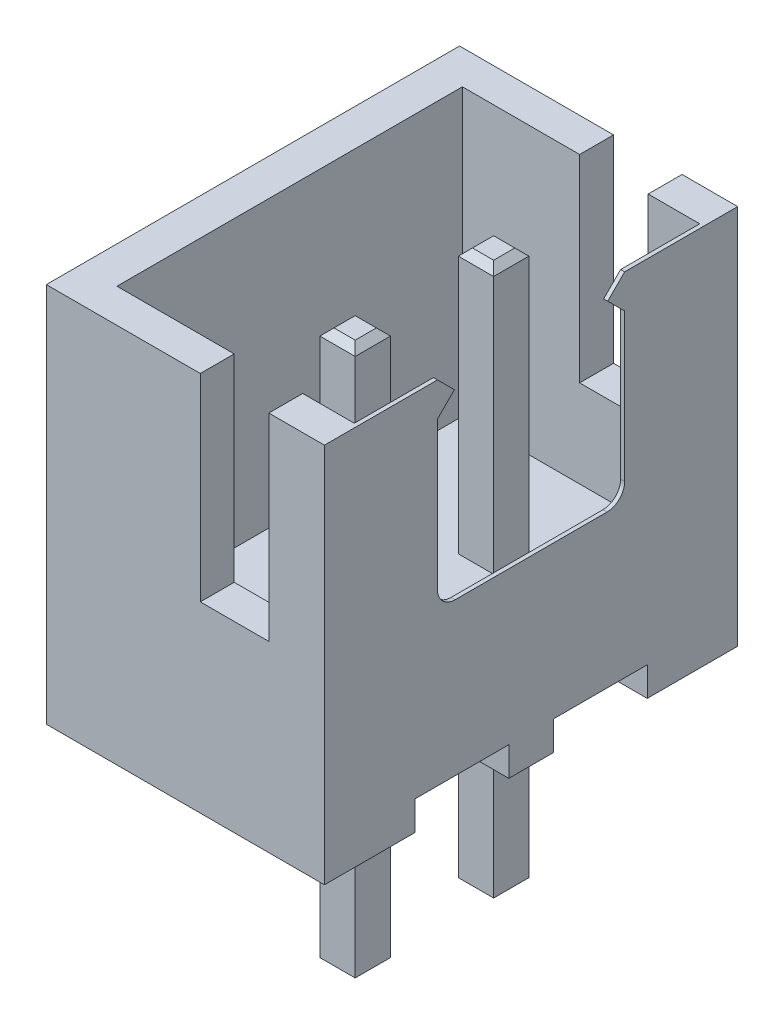
SolidWorks part; units mm, degrees
ref_plane "Front Plane" through (0, 0, 0) normal (0, 0, 1) x (1, 0, 0)
ref_plane "Top Plane" through (0, 0, 0) normal (0, 1, 0) x (1, 0, 0)
ref_plane "Right Plane" through (0, 0, 0) normal (1, 0, 0) x (0, 0, -1)
ref_plane "Plane1" through (-5.7277, 0, 0) normal (-1, 0, 0) x (0, -1, 0)
sketch "Sketch1" plane through (-5.7277, 0, 0) normal (-1, 0, 0) x (0, -1, 0)
  line L0 (-6.8453, -7.4295) -> (0, -7.4295)
  line L1 (0, -7.4295) -> (0, 0)
  line L2 (0, 0) -> (-6.8453, 0)
  line L3 (-6.8453, 0) -> (-6.8453, -7.4295)
extrude "Boss-Extrude1" add sketch "Sketch1" against normal blind 5
sketch "Sketch2" plane through (-5.7277, 0, 0) normal (-1, 0, 0) x (0, 0, 1)
  line L0 (-7.4295, 0) -> (-1.6256, 0)
  line L1 (-1.6256, 0) -> (-1.6256, 0.127)
  line L2 (-1.6256, 0.127) -> (-7.4295, 0.127)
  line L3 (-7.4295, 0.127) -> (-7.4295, 0)
extrude "Cut-Extrude1" cut sketch "Sketch2" against normal blind 5.7277
ref_plane "Plane2" through (0, 0, -1.6256) normal (0, 0, 1) x (1, 0, 0)
sketch "Sketch3" plane through (0, 0, -1.6256) normal (0, 0, 1) x (1, 0, 0)
  line L0 (-5.7277, 0.127) -> (-3.3477, 0.127)
  line L1 (-3.3477, 0.127) -> (-5.7277, 0.762)
  line L2 (-5.7277, 0.762) -> (-5.7277, 0.127)
  dimension "D1" = 2.38
extrude "Cut-Extrude2" cut sketch "Sketch3" against normal blind 1.6891
sketch "Sketch4" plane through (0, 0, -1.6256) normal (0, 0, 1) x (1, 0, 0)
  line L0 (-1.94, 0.127) -> (0, 0.127)
  line L1 (0, 0.127) -> (0, 0.762)
  line L2 (0, 0.762) -> (-1.94, 0.127)
  dimension "D1" = 1.94
extrude "Cut-Extrude3" cut sketch "Sketch4" against normal blind 1.6891
sketch "Sketch5" plane through (0, 0.127, 0) normal (0, -1, 0) x (1, 0, 0)
  line L0 (-5.7277, -7.4295) -> (-5.7277, -3.3147)
  line L1 (-5.7277, -3.3147) -> (-0.7277, -3.3147)
  line L2 (-0.7277, -3.3147) -> (-0.7277, -7.4295)
  line L3 (-0.7277, -7.4295) -> (-5.7277, -7.4295)
  dimension "D1" = 5
extrude "Boss-Extrude2" add sketch "Sketch5" along normal blind 0.127
sketch "Sketch6" plane through (-5.7277, 0, 0) normal (-1, 0, 0) x (0, 0, 1)
  line L0 (-7.4295, 0) -> (-4.1148, 0)
  line L1 (-4.1148, 0) -> (-4.1148, 0.127)
  line L2 (-4.1148, 0.127) -> (-7.4295, 0.127)
  line L3 (-7.4295, 0.127) -> (-7.4295, 0)
extrude "Cut-Extrude4" cut sketch "Sketch6" against normal through all
ref_plane "Plane3" through (0, 0, -4.1148) normal (0, 0, 1) x (1, 0, 0)
sketch "Sketch7" plane through (0, 0, -4.1148) normal (0, 0, 1) x (1, 0, 0)
  line L0 (-5.7277, 0.127) -> (-3.3477, 0.127)
  line L1 (-3.3477, 0.127) -> (-5.7277, 0.762)
  line L2 (-5.7277, 0.762) -> (-5.7277, 0.127)
  dimension "D1" = 2.38
extrude "Cut-Extrude5" cut sketch "Sketch7" against normal blind 1.6891
sketch "Sketch8" plane through (0, 0, -4.1148) normal (0, 0, 1) x (1, 0, 0)
  line L0 (-1.94, 0.127) -> (0, 0.127)
  line L1 (0, 0.127) -> (0, 0.762)
  line L2 (0, 0.762) -> (-1.94, 0.127)
  dimension "D1" = 1.94
extrude "Cut-Extrude6" cut sketch "Sketch8" against normal blind 1.6891
sketch "Sketch9" plane through (0, 0.127, 0) normal (0, -1, 0) x (1, 0, 0)
  line L0 (-5.7277, -5.8039) -> (-0.7277, -5.8039)
  line L1 (-0.7277, -5.8039) -> (-0.7277, -7.4295)
  line L2 (-0.7277, -7.4295) -> (-5.7277, -7.4295)
  line L3 (-5.7277, -7.4295) -> (-5.7277, -5.8039)
  dimension "D1" = 5
extrude "Boss-Extrude3" add sketch "Sketch9" along normal blind 0.127
sketch "Sketch10" plane through (0, 6.8453, 0) normal (0, 1, 0) x (-1, 0, 0)
  line L0 (5.0673, -6.8199) -> (5.0673, -0.6096)
  line L1 (5.0673, -0.6096) -> (0.8001, -0.6096)
  line L2 (0.8001, -0.6096) -> (0.8001, -6.8199)
  line L3 (0.8001, -6.8199) -> (5.0673, -6.8199)
extrude "Cut-Extrude7" cut sketch "Sketch10" against normal blind 5.1308
sketch "Sketch11" plane through (-0.8001, 0, 0) normal (-1, 0, 0) x (0, 0, 1)
  line L0 (-2.032, 6.8453) -> (-5.3975, 6.8453)
  line L1 (-5.3975, 6.8453) -> (-4.7879, 6.2357)
  line L2 (-4.7879, 6.2357) -> (-5.3975, 6.2357)
  line L3 (-5.3975, 6.2357) -> (-5.3975, 3.2639)
  line L4 (-5.3975, 3.2639) -> (-2.032, 3.2639)
  line L5 (-2.032, 3.2639) -> (-2.032, 6.2357)
  line L6 (-2.032, 6.2357) -> (-2.6416, 6.2357)
  line L7 (-2.6416, 6.2357) -> (-2.032, 6.8453)
extrude "Cut-Extrude8" cut sketch "Sketch11" against normal through all
sketch "Sketch12" plane through (0, 0, -0.6096) normal (0, 0, -1) x (-1, 0, 0)
  line L0 (2.9596, 6.8453) -> (1.7277, 6.8453)
  line L1 (1.7277, 6.8453) -> (1.7277, 3.2893)
  line L2 (1.7277, 3.2893) -> (2.9596, 3.2893)
  line L3 (2.9596, 3.2893) -> (2.9596, 6.8453)
  line L4 (0.7277, 0) -> (0.7277, 6.8453) construction
  dimension "D1" = 1
extrude "Cut-Extrude9" cut sketch "Sketch12" against normal through all
sketch "Sketch13" plane through (0, 0, -7.4295) normal (0, 0, -1) x (-1, 0, 0)
  line L0 (1.7277, 6.8453) -> (1.7277, 3.2893)
  line L1 (1.7277, 3.2893) -> (2.9596, 3.2893)
  line L2 (2.9596, 3.2893) -> (2.9596, 6.8453)
  line L3 (2.9596, 6.8453) -> (1.7277, 6.8453)
  line L4 (0.7277, 0) -> (0.7277, 6.8453) construction
  dimension "D1" = 1
extrude "Cut-Extrude10" cut sketch "Sketch13" against normal through all
sketch "Sketch14" plane through (0, 0.127, 0) normal (0, -1, 0) x (1, 0, 0)
  line L0 (-2.3277, -5.2768) -> (-2.9627, -5.2768)
  line L1 (-2.9627, -5.2768) -> (-2.9627, -4.6419)
  line L2 (-2.9627, -4.6419) -> (-2.3277, -4.6419)
  line L3 (-2.3277, -4.6419) -> (-2.3277, -5.2768)
  line L4 (-0.7277, -4.1148) -> (-0.7277, -5.8039) construction
  dimension "D1" = 1.6
extrude "Boss-Extrude4" add sketch "Sketch14" along normal blind 3.5814
sketch "Sketch15" plane through (0, 0.127, 0) normal (0, -1, 0) x (1, 0, 0)
  line L0 (-2.9627, -2.1527) -> (-2.3277, -2.1527)
  line L1 (-2.3277, -2.1527) -> (-2.3277, -2.7877)
  line L2 (-2.3277, -2.7877) -> (-2.9627, -2.7877)
  line L3 (-2.9627, -2.7877) -> (-2.9627, -2.1527)
  line L4 (-0.7277, -1.6256) -> (-0.7277, -3.3147) construction
  dimension "D1" = 1.6
extrude "Boss-Extrude5" add sketch "Sketch15" along normal blind 3.5814
sketch "Sketch16" plane through (0, 1.7145, 0) normal (0, 1, 0) x (-1, 0, 0)
  line L0 (2.9627, -4.6419) -> (2.9627, -5.2768)
  line L1 (2.9627, -5.2768) -> (2.3277, -5.2768)
  line L2 (2.3277, -5.2768) -> (2.3277, -4.6419)
  line L3 (2.3277, -4.6419) -> (2.9627, -4.6419)
  line L4 (0.7277, -5.3975) -> (0.7277, -2.032) construction
  dimension "D1" = 1.6
extrude "Boss-Extrude6" add sketch "Sketch16" along normal blind 4.7625
sketch "Sketch17" plane through (0, 1.7145, 0) normal (0, 1, 0) x (-1, 0, 0)
  line L0 (2.3277, -2.1526) -> (2.9627, -2.1526)
  line L1 (2.9627, -2.1526) -> (2.9627, -2.7877)
  line L2 (2.9627, -2.7877) -> (2.3277, -2.7877)
  line L3 (2.3277, -2.7877) -> (2.3277, -2.1526)
  line L4 (0.7277, -5.3975) -> (0.7277, -2.032) construction
  dimension "D1" = 1.6
extrude "Boss-Extrude7" add sketch "Sketch17" along normal blind 4.7625
draft "Draft1" type of draft neutral plane draft angle 45 faces to draft 1 face at (-0.7639, 6.2357, -2.3368) neutral plane through (-0.7277, 3.2639, -2.032) neutral plane normal (0, 0, -1) parameters "D1"=45
draft "Draft2" type of draft neutral plane draft angle 45 faces to draft 1 face at (-0.7639, 6.2357, -5.0927) neutral plane through (-0.7277, 6.2357, -5.3975) neutral plane normal (0, 0, 1) parameters "D1"=45
chamfer "Chamfer1" distance 0.127 angle 45 16 edges at (-2.9627, -3.4544, -4.9593) (-2.6452, -3.4544, -4.6419) (-2.6452, -3.4544, -5.2768) (-2.3277, -3.4544, -4.9593) (-2.9627, 6.477, -2.4701) (-2.6452, 6.477, -2.7877) (-2.6452, 6.477, -2.1526) (-2.3277, 6.477, -2.4701) (-2.6452, 6.477, -5.2768) (-2.9627, 6.477, -4.9593) (-2.3277, 6.477, -4.9593) (-2.6452, 6.477, -4.6419) (-2.3277, -3.4544, -2.4701) (-2.6452, -3.4544, -2.7877) (-2.6452, -3.4544, -2.1527) (-2.9627, -3.4544, -2.4701)
fillet "Fillet1" radius 0.3175 2 edges at (-0.7639, 3.2639, -2.032) (-0.7639, 3.2639, -5.3975) tangent propagation no
ref_plane "Plane4" through (0, 0, 0) normal (0, -1, 0) x (-1, 0, 0)
sketch "Sketch18" plane through (0, 0, 0) normal (0, -1, 0) x (-1, 0, 0)
  line L0 (2.4547, 4.7688) -> (2.8357, 4.7688) construction
  line L1 (0.7277, 4.1148) -> (0.7277, 3.3147) construction
  point P0 (2.6452, 3.7147)
  point P4 (2.6452, 4.7688)
  point P8 (0.7277, 3.7147)
ref_plane "Plane14" through (-2.2277, 0, 0) normal (1, 0, 0) x (0, 0, -1)
sketch "Sketch19" plane through (-2.2277, 0, 0) normal (1, 0, 0) x (0, 0, -1)
  line L0 (2.7877, 6.35) -> (2.1526, 6.35) construction
  line L1 (5.2768, 6.35) -> (4.6419, 6.35) construction
  point P0 (2.4701, 7.0456)
  point P1 (2.4701, 7.8077)
  point P2 (4.9593, 7.0456)
  point P3 (4.9777, 7.8077)
  point P4 (2.4701, 5.6926)
  point P7 (2.4701, 6.35)
  point P12 (4.9593, 6.35)
  point P18 (4.9593, 5.6926)
